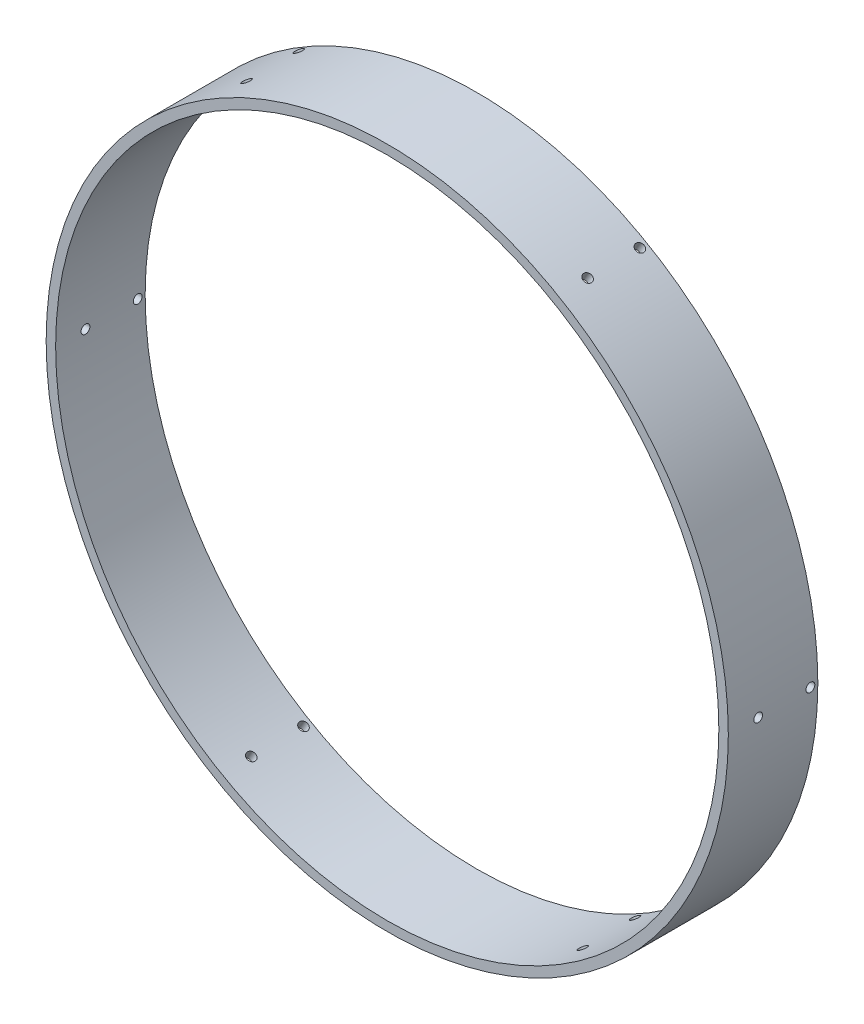
SolidWorks part; units mm, degrees
material "6061-T6 (SS)"
ref_plane "Front Plane" through (0, 0, 0) normal (0, 0, 1) x (1, 0, 0)
ref_plane "Top Plane" through (0, 0, 0) normal (0, 1, 0) x (1, 0, 0)
ref_plane "Right Plane" through (0, 0, 0) normal (1, 0, 0) x (0, 0, -1)
sketch "Sketch1" plane through (0, 0, 0) normal (0, 0, 1) x (1, 0, 0)
  circle A0 centre (0, 0) radius 114.3
  circle A1 centre (0, 0) radius 107.95
  dimension "D1" = 228.6
  dimension "D2" = 6.35
extrude "Boss-Extrude1" add sketch "Sketch1" along normal blind 320
ref_plane "Plane1" through (-114.3, 0, 0) normal (-1, 0, 0) x (0, 0, 1)
sketch "Sketch2" plane through (-114.3, 0, 0) normal (-1, 0, 0) x (0, 0, 1)
  line L0 (0, 0) -> (320, 0) construction
  line L1 (0, 114.3) -> (0, -114.3) construction
  line L2 (320, -114.3) -> (320, 114.3) construction
  circle A0 centre (2.5, 0) radius 1.4732
  circle A1 centre (310, 0) radius 1.4732
  circle A2 centre (292.5, 0) radius 1.4732
  dimension "D1" = 2.5
  dimension "D2" = 2.9464
  dimension "D3" = 10
  dimension "D4" = 2.9464
  dimension "D5" = 2.9464
  dimension "D6" = 27.5
extrude "Cut-Extrude1" cut sketch "Sketch2" against normal through all
ref_axis "Axis1" through (0, 0, 320) along (0, 0, -1)
pattern_circular "CirPattern1" count 3 over 360 about axis through (0, 0, 320) along (0, 0, -1) of "Cut-Extrude1"
sketch "Sketch3" plane through (0, 0, 320) normal (0, 0, 1) x (1, 0, 0)
  circle A1 centre (0, 0) radius 114.3
  circle A2 centre (0, 0) radius 114.3
  circle A4 centre (0, 0) radius 111.125
  circle A5 centre (0, 0) radius 111.125
  circle M4 centre (0, 0) radius 107.95
  dimension "D1" = 0
  dimension "D2" = 3.175
extrude "Cut-Extrude2" cut sketch "Sketch3" against normal blind 40 contours A5 M4 region at (-107.9819, 0, 320)
sketch "Sketch4" plane through (0, 0, 0) normal (0, 0, -1) x (-1, 0, 0)
  circle A1 centre (0, 0) radius 114.3
  circle A2 centre (0, 0) radius 114.3
  circle A4 centre (0, 0) radius 111.125
  circle A5 centre (0, 0) radius 111.125
  circle M4 centre (0, 0) radius 107.95
  dimension "D1" = 0
  dimension "D2" = 3.175
extrude "Cut-Extrude3" cut sketch "Sketch4" against normal blind 10 contours A5 M4 region at (107.9819, 0, 0)
ref_axis "Axis2" through (-24.7009, 0, 2.5) along (-1, 0, 0)
ref_plane "Plane2" through (-113.8651, 9.9619, 0) normal (-0.9962, 0.0872, 0) x (0, 0, 1)
ref_plane "Plane3" through (-113.8651, -9.9619, 0) normal (-0.9962, -0.0872, 0) x (0, 0, 1)
sketch "Sketch6" plane through (-113.8651, 9.9619, 0) normal (-0.9962, 0.0872, 0) x (0, 0, 1)
  line L1 (320, 0) -> (260.79, 0) construction
  line L2 (320, -114.3) -> (320, 114.3) construction
  circle A1 centre (260.79, 0) radius 1.4732
  dimension "D4" = 2.9464
  dimension "D3" = 59.21
extrude "Cut-Extrude4" cut sketch "Sketch6" against normal blind 10
sketch "Sketch7" plane through (-113.8651, -9.9619, 0) normal (-0.9962, -0.0872, 0) x (0, 0, 1)
  line L1 (320, 0) -> (260.79, 0) construction
  line L2 (320, -114.3) -> (320, 114.3) construction
  circle A1 centre (260.79, 0) radius 1.4732
  dimension "D4" = 2.9464
  dimension "D3" = 59.21
extrude "Cut-Extrude5" cut sketch "Sketch7" against normal blind 10
pattern_circular "CirPattern3" count 3 over 360 about axis through (0, 0, 320) along (0, 0, -1) of "Cut-Extrude5", "Cut-Extrude4"
ref_plane "Plane4" through (-57.15, 98.9867, 0) normal (-0.5, 0.866, 0) x (0, 0, 1)
sketch "Sketch8" plane through (-57.15, 98.9867, 0) normal (-0.5, 0.866, 0) x (0, 0, 1)
  line L0 (0, 0) -> (320, 0) construction
  line L1 (320, -114.3) -> (320, 114.3) construction
  line L2 (0, 114.3) -> (0, -114.3) construction
  circle A0 centre (20, 0) radius 1.4732
  circle A1 centre (259.803, 0) radius 1.4732
  dimension "D2" = 60.197
  dimension "D3" = 2.9464
  dimension "D4" = 2.9464
  dimension "D1" = 20
extrude "Cut-Extrude6" cut sketch "Sketch8" against normal blind 10
pattern_circular "CirPattern4" count 3 over 360 about axis through (0, 0, 320) along (0, 0, -1) of "Cut-Extrude6"
sketch "Sketch9" plane through (0, 0, 0) normal (1, 0, 0) x (0, 0, -1)
  line L0 (-320, -114.3) -> (0, -114.3) construction
  line L1 (0, 114.3) -> (-290, 114.3)
  line L2 (0, 114.3) -> (0, -114.3)
  line L3 (0, -114.3) -> (-290, -114.3)
  line L4 (-290, 114.3) -> (-290, -114.3)
  line L5 (-320, 114.3) -> (-320, -114.3) construction
  dimension "D1" = 30
extrude "Cut-Extrude7" cut sketch "Sketch9" against normal through all and the other way through all
